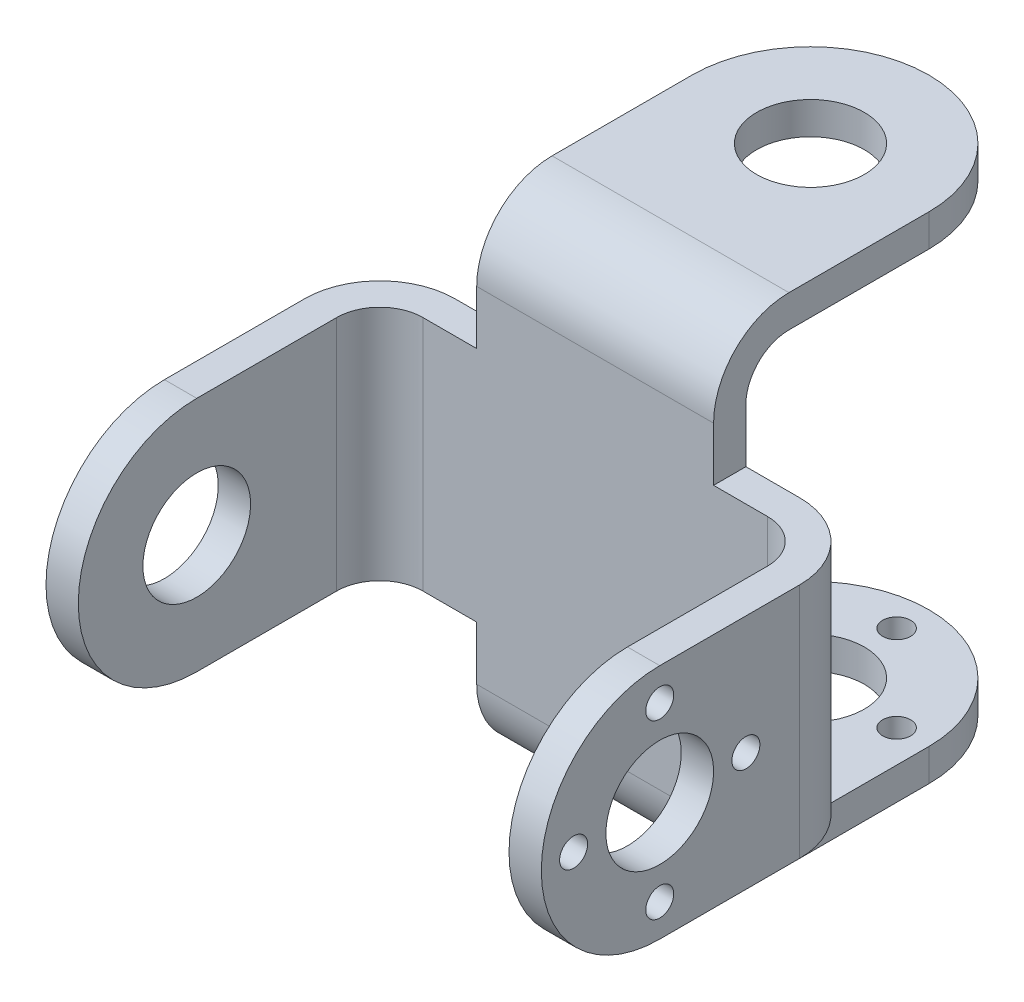
SolidWorks part; units mm, degrees
note: The reader was unsure of these and kept them because the rebuilt part matched: shared geometry of "Sketch2<4>".
ref_plane "Front Plane" through (0, 0, 0) normal (0, 0, 1) x (1, 0, 0)
ref_plane "Top Plane" through (0, 0, 0) normal (0, 1, 0) x (1, 0, 0)
ref_plane "Right Plane" through (0, 0, 0) normal (1, 0, 0) x (0, 0, -1)
sketch "Sketch1" plane through (0, 0, 0) normal (0, 1, 0) x (1, 0, 0)
  line L1 (-11, 0) -> (11, 0)
  line L2 (-11, 0) -> (-11, -13)
  line L3 (-11, -13) -> (11, -13)
  line L4 (11, 0) -> (11, -13)
  circle A0 centre (0, 0) radius 11
  circle A2 centre (0, 0) radius 5
  dimension "D3" = 22
  dimension "D4" = 10
  dimension "D5" = 13
extrude "Boss-Extrude1" add sketch "Sketch1" along normal blind 3
sketch "Sketch2" plane through (11, 0, 0) normal (1, 0, 0) x (0, 0, -1)
  line L0 (-13, 3) -> (-13, 0)
  line L6 (-17, -36) -> (-9, -36) construction
  line L7 (-20, -4) -> (-17, -4)
  line L8 (-20, -4) -> (-20, -36)
  line L9 (-20, -36) -> (-17, -36)
  line L10 (-17, -4) -> (-17, -36)
  line L11 (-13, -43) -> (-13, -40)
  line L12 (-17, -36) -> (-20, -36)
  line L13 (-13, 0) -> (-13, 3)
  line L14 (-17, -4) -> (-20, -4)
  arc A0 (-13, 0) -> (-17, -4) centre (-13, -4) ccw
  arc A1 (-13, 3) -> (-20, -4) centre (-13, -4) ccw
  arc A4 (-17, -36) -> (-13, -40) centre (-13, -36) ccw
  arc A5 (-20, -36) -> (-13, -43) centre (-13, -36) ccw
  dimension "D1" = 4
  dimension "D2" = 4
  dimension "D3" = 4
  dimension "D4" = 4
  dimension "D5" = 32
extrude "Boss-Extrude2" add sketch "Sketch2" against normal up to surface (22 mm away) up to face at (-11, 1.5, 6.5)
extrude "Boss-Extrude10" add sketch "Sketch2<4>" against normal up to surface (22 mm away) contours L9 A5 L11 A4 up to face at (-11, -8.9652, 12.7848)
sketch "Sketch2<4>" plane through (11, 0, 0) normal (1, 0, 0) x (0, 0, -1) same geometry as "Sketch2"
ref_plane "Plane1" through (0, -40, 0) normal (0, -1, 0) x (-1, 0, 0)
sketch "Sketch3" plane through (0, -40, 0) normal (0, -1, 0) x (-1, 0, 0)
  line L1 (-11, 0) -> (11, 0)
  line L2 (-11, 0) -> (-11, -13)
  line L3 (-11, -13) -> (11, -13)
  line L4 (11, 0) -> (11, -13)
  circle A0 centre (0, 0) radius 5
  circle A1 centre (0, 0) radius 11
  circle A2 centre (0, 0) radius 8 construction
  circle A3 centre (0, 8) radius 1.3
  circle A4 centre (8, 0) radius 1.3
  circle A5 centre (0, -8) radius 1.3
  circle A6 centre (-8, 0) radius 1.3
  dimension "D1" = 16
  dimension "D2" = 2.6
extrude "Boss-Extrude3" add sketch "Sketch3" along normal blind 3 contours A1 L2 L3 L4 | L1 A1 A0 | L1 A1 A0
sketch "Sketch5" plane through (0, 0, 20) normal (0, 0, 1) x (1, 0, 0)
  line L0 (-11, -4) -> (11, -4) construction
  line L6 (-11, -36) -> (-11, -4) construction
  line L7 (-11, -20) -> (11, -20) construction
  line L8 (11, -4) -> (11, -36) construction
  line L9 (0, -4) -> (0, -36) construction
  line L11 (-16, -9) -> (16, -9)
  line L12 (-16, -9) -> (-16, -31)
  line L13 (-16, -31) -> (16, -31)
  line L14 (16, -9) -> (16, -31)
  line L15 (-16, -9) -> (16, -31) construction
  line L16 (-16, -31) -> (16, -9) construction
  point P0 (0, -20)
  dimension "D1" = 32
  dimension "D2" = 22
extrude "Boss-Extrude4" add sketch "Sketch5" against normal up to surface (3 mm away) up to face at (0, -20, 17)
sketch "Sketch6" plane through (0, -9, 0) normal (0, 1, 0) x (1, 0, 0)
  line L0 (-23, -24) -> (-20, -24)
  line L1 (20, -24) -> (23, -24)
  line L2 (-16, -20) -> (-16, -17)
  line L3 (16, -17) -> (16, -20)
  arc A0 (-16, -20) -> (-20, -24) centre (-16, -24) ccw
  arc A1 (-16, -17) -> (-23, -24) centre (-16, -24) ccw
  arc A2 (16, -20) -> (20, -24) centre (16, -24) cw
  arc A3 (16, -17) -> (23, -24) centre (16, -24) cw
  dimension "D1" = 4
  dimension "D2" = 4
  dimension "D3" = 4
  dimension "D4" = 4
extrude "Boss-Extrude5" add sketch "Sketch6" against normal up to surface (22 mm away) up to face at (13.5, -31, 18.5)
ref_plane "Plane2" through (23, 0, 0) normal (-1, 0, 0) x (0, 0, 1)
sketch "Sketch8" plane through (23, 0, 0) normal (-1, 0, 0) x (0, 0, 1)
  line L1 (24, -9) -> (37, -9)
  line L2 (24, -9) -> (24, -31)
  line L3 (24, -31) -> (37, -31)
  line L4 (37, -9) -> (37, -31)
  circle A0 centre (37, -20) radius 11
  circle A1 centre (37, -20) radius 8 construction
  circle A2 centre (37, -20) radius 5
  circle A3 centre (29, -20) radius 1.3
  circle A4 centre (37, -28) radius 1.3
  circle A5 centre (45, -20) radius 1.3
  circle A6 centre (37, -12) radius 1.3
  dimension "D2" = 2.6
  dimension "D3" = 10
  dimension "D4" = 16
  dimension "D5" = 22
  dimension "D1" = 13
extrude "Boss-Extrude8" add sketch "Sketch8" along normal blind 3 contours A0 L1 L2 L3 | A6 L4 A0 A4 A2 A3 | A6 L4 A2 A4 A0 A5
ref_plane "Plane3" through (-23, 0, 0) normal (-1, 0, 0) x (0, 0, 1)
sketch "Sketch9" plane through (-23, 0, 0) normal (-1, 0, 0) x (0, 0, 1)
  line L1 (24, -31) -> (37, -31)
  line L2 (24, -31) -> (24, -9)
  line L3 (24, -9) -> (37, -9)
  line L4 (37, -31) -> (37, -9)
  circle A0 centre (37, -20) radius 11
  circle A1 centre (37, -20) radius 5
  dimension "D2" = 22
  dimension "D3" = 10
  dimension "D1" = 13
extrude "Boss-Extrude9" add sketch "Sketch9" against normal blind 3 contours A0 L3 L2 L1 | A1 L4 A0 | A1 L4 A0
